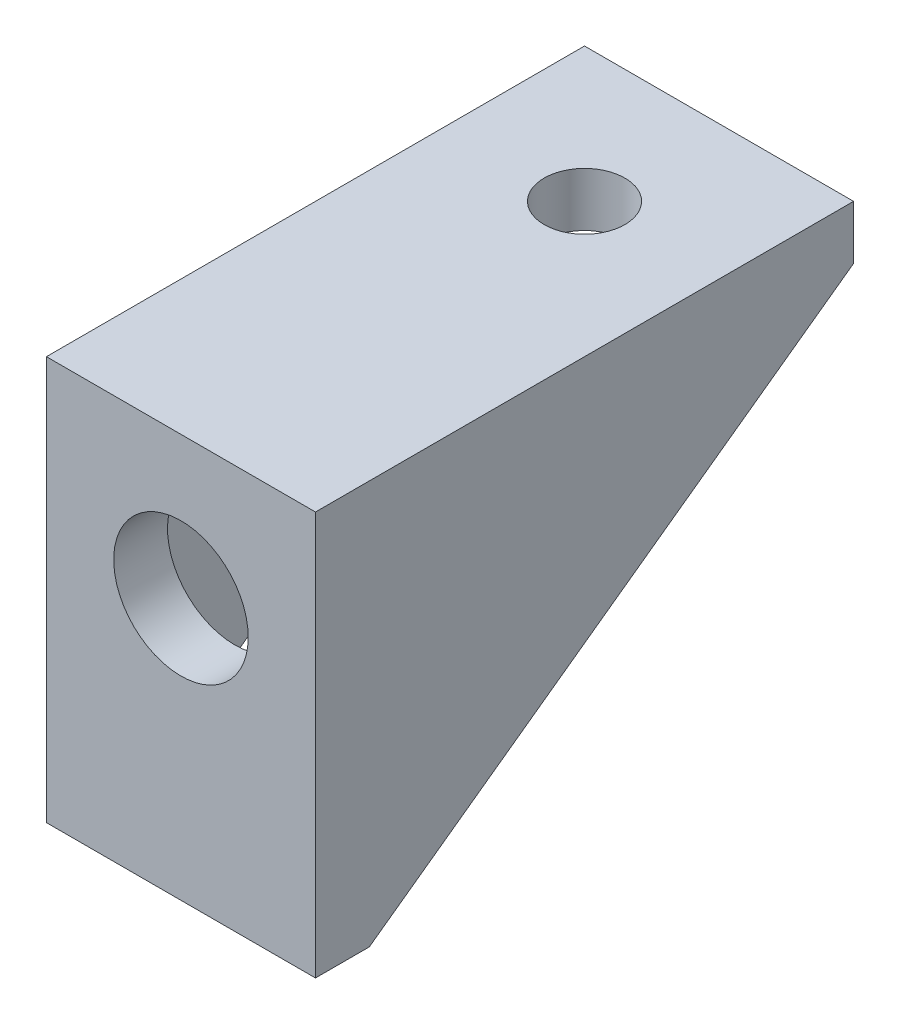
SolidWorks part; units mm, degrees
ref_plane "Front Plane" through (0, 0, 0) normal (0, 0, 1) x (1, 0, 0)
ref_plane "Top Plane" through (0, 0, 0) normal (0, 1, 0) x (1, 0, 0)
ref_plane "Right Plane" through (0, 0, 0) normal (1, 0, 0) x (0, 0, -1)
sketch "Sketch1" plane through (0, 0, 0) normal (1, 0, 0) x (0, 0, -1)
  line L0 (0, 0) -> (20, 0)
  line L1 (0, 0) -> (0, -15)
  line L2 (2, -2) -> (2, -15)
  line L11 (2, -2) -> (20, -2)
  line L12 (0, -15) -> (2, -15)
  line L13 (20, 0) -> (20, -2)
  dimension "D1" = 20
  dimension "D2" = 15
  dimension "D3" = 2
extrude "Boss-Extrude1" add sketch "Sketch1" along normal blind 10
sketch "Sketch2" plane through (0, 0, 0) normal (0, 0, 1) x (1, 0, 0)
  line L0 (0, 0) -> (0, -15) construction
  line L1 (10, 0) -> (0, 0) construction
  circle A0 centre (5, -5.28) radius 2.5
  point P6 (4.4562, -0.1122)
  dimension "D3" = 5
  dimension "D1" = 5
  dimension "D2" = 5.28
extrude "Cut-Extrude1" cut sketch "Sketch2" against normal up to next
sketch "Sketch3" plane through (0, 0, 0) normal (0, 1, 0) x (1, 0, 0)
  line L1 (10, 20) -> (0, 20) construction
  line L3 (10, 0) -> (0, 0) construction
  line L4 (0, 20) -> (0, 0) construction
  circle A1 centre (5, 15) radius 1.5
  point P9 (0, 0)
  point P13 (5, 0)
  dimension "D1" = 5
  dimension "D3" = 3
  dimension "D2" = 5
extrude "Cut-Extrude2" cut sketch "Sketch3" against normal up to next
sketch "Sketch5" plane through (10, 0, 0) normal (1, 0, 0) x (0, 0, -1)
  line L0 (20, -2) -> (2, -15)
  line L1 (2, -15) -> (2, -2)
  line L2 (2, -2) -> (20, -2)
extrude "Boss-Extrude2" add sketch "Sketch5" against normal blind 1
ref_plane "Plane1" through (5, 0, 0) normal (-1, 0, 0) x (0, 0, 1)
mirror "Mirror1" about plane through (5, 0, 0) normal (-1, 0, 0) of "Boss-Extrude2"
